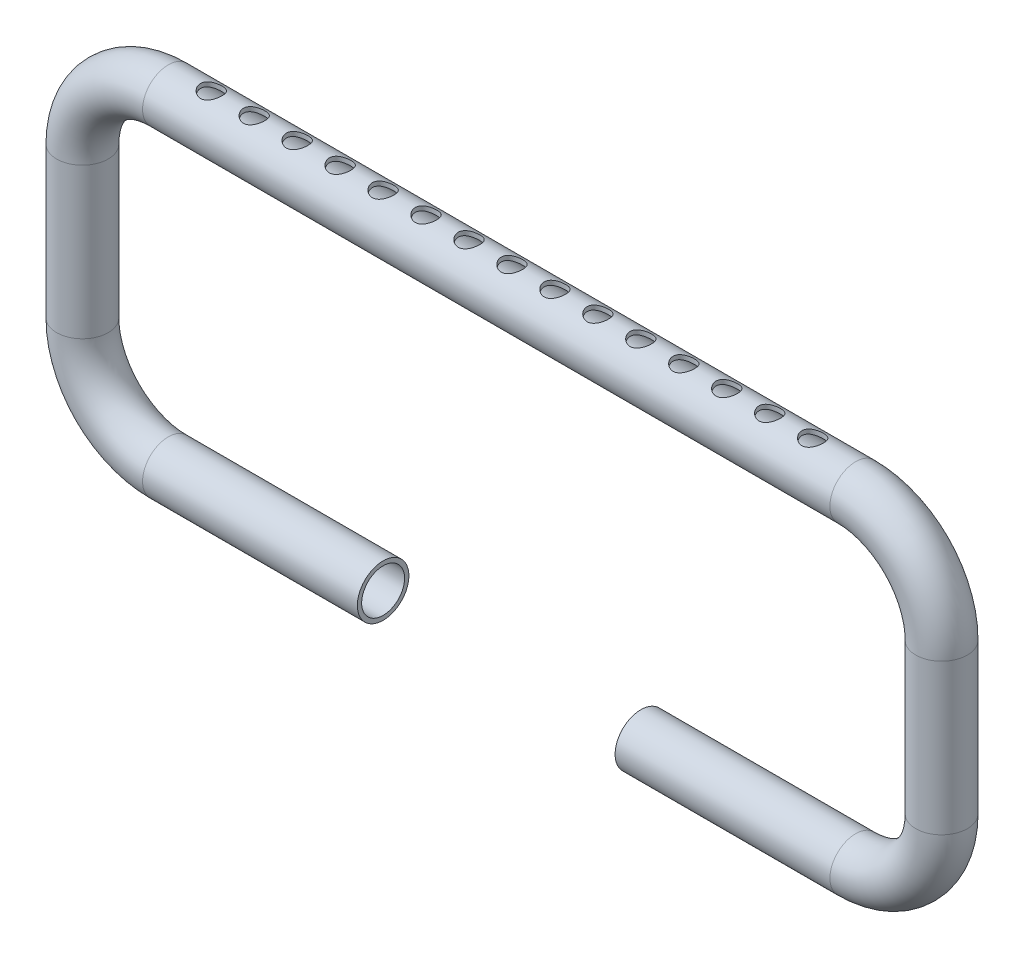
SolidWorks part; units mm, degrees
material "ABS"
ref_plane "Front Plane" through (0, 0, 0) normal (0, 0, 1) x (1, 0, 0)
ref_plane "Top Plane" through (0, 0, 0) normal (0, 1, 0) x (1, 0, 0)
ref_plane "Right Plane" through (0, 0, 0) normal (1, 0, 0) x (0, 0, -1)
sketch "Sketch1" plane through (0, 0, 0) normal (1, 0, 0) x (0, 0, -1)
  circle A0 centre (0, 0) radius 6
  circle A1 centre (0, 0) radius 5
  dimension "D1" = 10
  dimension "D2" = 1
sketch "Sketch2" plane through (0, 0, 0) normal (0, 0, 1) x (1, 0, 0)
  line L0 (0, 0) -> (-50, 0)
  line L1 (-70, 20) -> (-70, 55)
  line L2 (-50, 75) -> (110, 75)
  line L3 (130, 55) -> (130, 20)
  line L4 (110, 0) -> (60, 0)
  line L5 (30, 75) -> (30, 0) construction
  arc A0 (130, 55) -> (110, 75) centre (110, 55) ccw
  arc A1 (110, 0) -> (130, 20) centre (110, 20) ccw
  arc A2 (-70, 20) -> (-50, 0) centre (-50, 20) ccw
  arc A3 (-70, 55) -> (-50, 75) centre (-50, 55) cw
  point P9 (130, 75)
  point P14 (-70, 0)
  point P17 (-70, 75)
  point P18 (0, 0)
  point P19 (30, 47.4753)
  point P20 (30, 0)
  dimension "D3" = 20
  dimension "D1" = 200
  dimension "D2" = 75
  dimension "D4" = 30
  dimension "D5" = 60
  dimension "D6" = 75
sweep "Sweep1" add profiles "Sketch1" path "Sketch2"
ref_plane "Plane1" through (0, 81, 0) normal (0, 1, 0) x (1, 0, 0)
sketch "Sketch3" plane through (0, 81, 0) normal (0, 1, 0) x (1, 0, 0)
  line L0 (110, 6) -> (110, -6)
  line L1 (110, 6) -> (110, -6) construction
  line L2 (110, 0) -> (-47.2973, 0)
  circle A0 centre (100, 0) radius 2.5
  circle A1 centre (90, 0) radius 2.5
  circle A2 centre (80, 0) radius 2.5
  circle A3 centre (70, 0) radius 2.5
  circle A4 centre (60, 0) radius 2.5
  circle A5 centre (50, 0) radius 2.5
  circle A6 centre (40, 0) radius 2.5
  circle A7 centre (30, 0) radius 2.5
  circle A8 centre (20, 0) radius 2.5
  circle A9 centre (10, 0) radius 2.5
  circle A10 centre (0, 0) radius 2.5
  circle A11 centre (-10, 0) radius 2.5
  circle A12 centre (-20, 0) radius 2.5
  circle A13 centre (-30, 0) radius 2.5
  circle A14 centre (-40, 0) radius 2.5
  point P10 (0, 0)
  point P11 (0, 0)
  point P40 (0, 0)
  dimension "D2" = 5
  dimension "D1" = 10
  dimension "D3" = 15
extrude "Cut-Extrude1" cut sketch "Sketch3" against normal blind 15 contours A0 | A1 | A2 | A3 | A4 | A5 | A6 | A7 | A8 | A9 | A10 | A11 | A12 | A13 | A14
